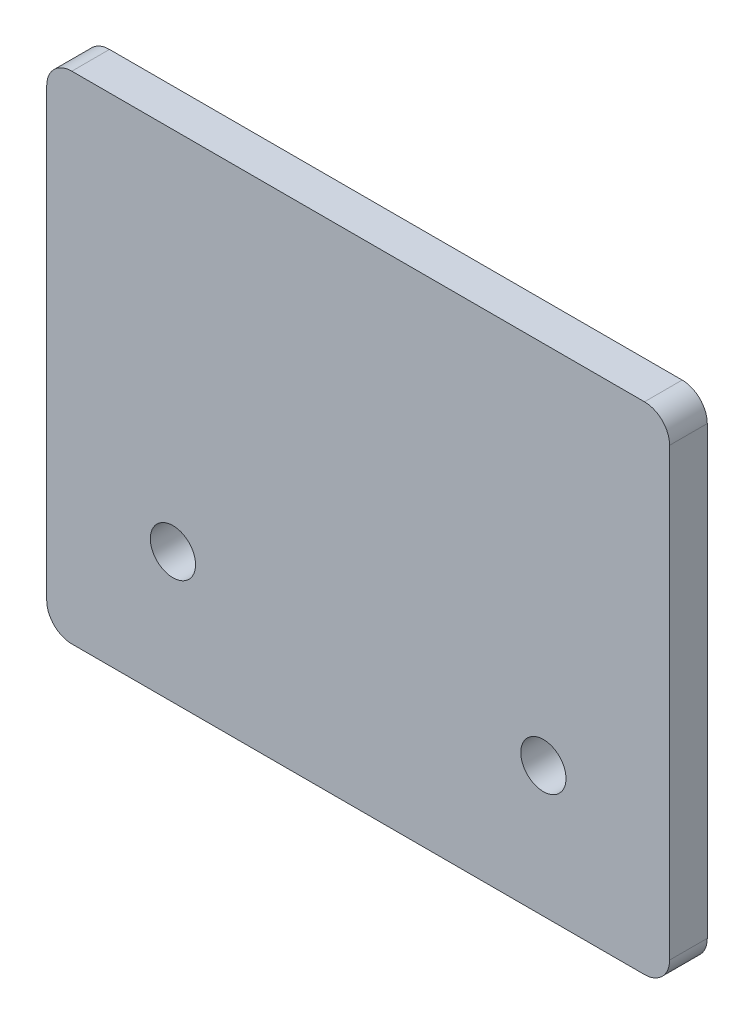
SolidWorks part; units mm, degrees
ref_plane "Front Plane" through (0, 0, 0) normal (0, 0, 1) x (1, 0, 0)
ref_plane "Top Plane" through (0, 0, 0) normal (0, 1, 0) x (1, 0, 0)
ref_plane "Right Plane" through (0, 0, 0) normal (1, 0, 0) x (0, 0, -1)
sketch "Sketch1" plane through (0, 0, 0) normal (0, 0, 1) x (1, 0, 0)
  line L1 (-67.8128, 8.2114) -> (-18.2128, 8.2114)
  line L2 (-67.8128, 8.2114) -> (-67.8128, 48.2114)
  line L3 (-67.8128, 48.2114) -> (-18.2128, 48.2114)
  line L4 (-18.2128, 8.2114) -> (-18.2128, 48.2114)
  circle A4 centre (-28.2628, 19.1013) radius 1.8 construction
  circle A5 centre (-57.7628, 19.1013) radius 1.8 construction
  circle A6 centre (-28.2628, 19.1013) radius 1.8
  circle A7 centre (-57.7628, 19.1013) radius 1.8
  dimension "D1" = 49.6
  dimension "D2" = 40
extrude "Boss-Extrude1" add sketch "Sketch1" along normal blind 3
sketch "Sketch2" plane through (0, 8.2114, 0) normal (0, -1, 0) x (1, 0, 0)
  line L4 (-67.8128, 0) -> (-18.2128, 0)
  line L5 (-18.2128, 0) -> (-18.2128, 3)
  line L6 (-18.2128, 3) -> (-67.8128, 3)
  line L7 (-67.8128, 3) -> (-67.8128, 0)
  line L8 (-67.8128, 0) -> (-18.2128, 0)
  line L9 (-18.2128, 0) -> (-18.2128, 3)
  line L10 (-18.2128, 3) -> (-67.8128, 3)
  line L11 (-67.8128, 3) -> (-67.8128, 0)
  dimension "D1" = 0
extrude "Cut-Extrude1" cut sketch "Sketch2" against normal blind 0.5
fillet "Fillet1" radius 2 4 edges at (-18.2128, 48.2114, 1.5) (-18.2128, 8.7114, 1.5) (-67.8128, 48.2114, 1.5) (-67.8128, 8.7114, 1.5)
